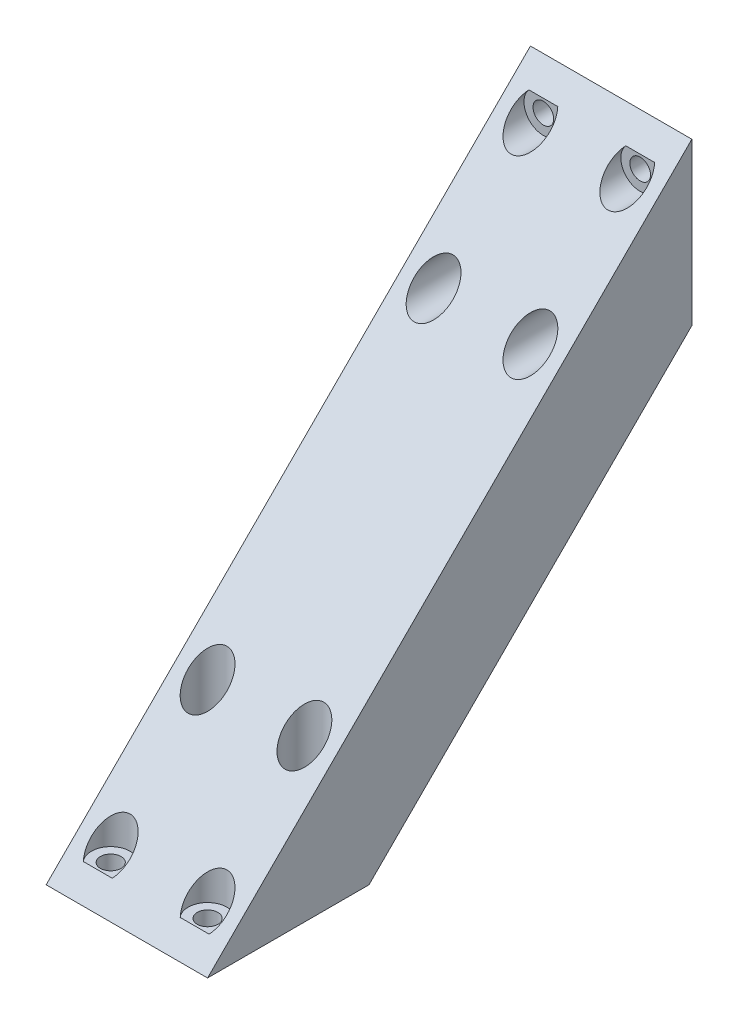
SolidWorks part; units mm, degrees
ref_plane "Front Plane" through (0, 0, 0) normal (0, 0, 1) x (1, 0, 0)
ref_plane "Top Plane" through (0, 0, 0) normal (0, 1, 0) x (1, 0, 0)
ref_plane "Right Plane" through (0, 0, 0) normal (1, 0, 0) x (0, 0, -1)
sketch "Sketch1" plane through (0, 0, 0) normal (1, 0, 0) x (0, 0, -1)
  line L0 (0, 40.3987) -> (0, -50) construction
  line L1 (0, 0) -> (-50, -50)
  line L2 (0, -50) -> (-50, -50) construction
  line L3 (-50, -50) -> (-75, -50)
  line L4 (-75, -50) -> (0, 25)
  line L5 (0, 25) -> (0, 0)
  dimension "D1" = 45
  dimension "D2" = 50
  dimension "D3" = 25
extrude "Boss-Extrude1" add sketch "Sketch1" along normal blind 25
sketch "Sketch2" plane through (0, -50, 0) normal (0, -1, 0) x (1, 0, 0)
  line L0 (25, 75) -> (0, 75) construction
  line L1 (25, 75) -> (25, 50) construction
  line L2 (20, 70) -> (5, 70) construction
  circle A0 centre (20, 70) radius 1.6
  circle A1 centre (20, 70) radius 3
  circle A2 centre (5, 70) radius 3
  circle A3 centre (5, 70) radius 1.6
  circle A4 centre (5, 55) radius 3
  circle A5 centre (5, 55) radius 1.6
  circle A6 centre (20, 55) radius 3
  circle A7 centre (20, 55) radius 1.6
  dimension "D1" = 6
  dimension "D2" = 3.2
  dimension "D3" = 5
  dimension "D4" = 5
  dimension "D7" = 15
  dimension "D5" = 2
  dimension "D6" = 2
extrude "Cut-Extrude2" cut sketch "Sketch2" against normal up to next from offset 3 contours A2 A3 | A0 A1 | A6 A7 | A4 A5 region at (17.0849, -50, 70) region at (2.0849, -50, 70) region at (2.0849, -50, 55) region at (17.0849, -50, 55) offset against normal yes
extrude "Cut-Extrude3" cut sketch "Sketch2<3>" against normal up to next contours A0 | A7 | A5 | A3 region at (20, -50, 70) region at (5, -50, 70) region at (5, -50, 55) region at (20, -50, 55)
sketch "Sketch2<3>" plane through (0, -50, 0) normal (0, -1, 0) x (1, 0, 0) same geometry as "Sketch2"
sketch "Sketch3" plane through (0, 0, 0) normal (0, 0, -1) x (-1, 0, 0)
  line L0 (-25, 0) -> (-25, 25) construction
  line L1 (-25, 25) -> (0, 25) construction
  line L2 (-20, 20) -> (-20, 5) construction
  circle A0 centre (-20, 20) radius 1.6
  circle A1 centre (-20, 20) radius 3
  circle A2 centre (-20, 5) radius 3
  circle A3 centre (-20, 5) radius 1.6
  circle A4 centre (-5, 5) radius 3
  circle A5 centre (-5, 5) radius 1.6
  circle A6 centre (-5, 20) radius 3
  circle A7 centre (-5, 20) radius 1.6
  dimension "D1" = 6
  dimension "D2" = 3.2
  dimension "D3" = 5
  dimension "D4" = 5
  dimension "D7" = 15
  dimension "D5" = 2
  dimension "D6" = 2
extrude "Cut-Extrude7" cut sketch "Sketch3" against normal up to next from offset 3 offset against normal yes
extrude "Cut-Extrude8" cut sketch "Sketch3<3>" against normal up to next contours A7 | A0 | A5 | A3 region at (20, 20, 0) region at (20, 5, 0) region at (5, 5, 0) region at (5, 20, 0)
sketch "Sketch3<3>" plane through (0, 0, 0) normal (0, 0, -1) x (-1, 0, 0) same geometry as "Sketch3"
